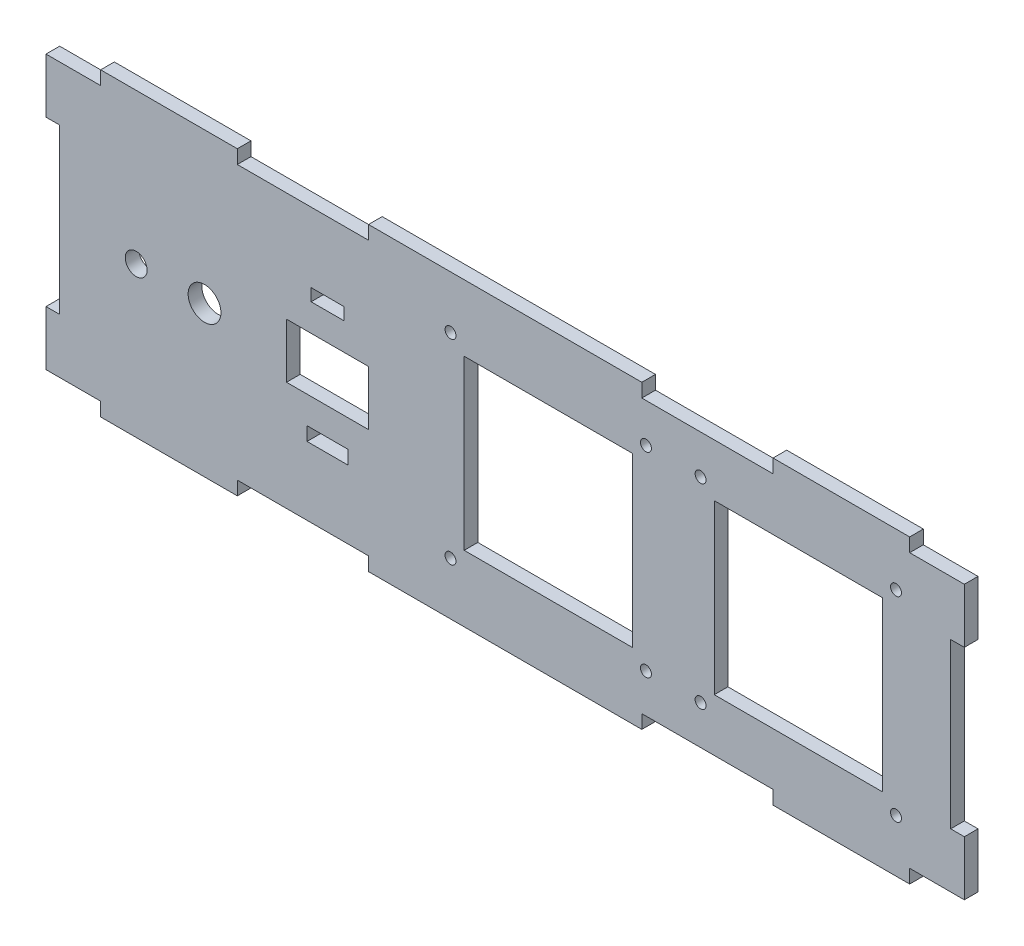
SolidWorks part; units mm, degrees
ref_plane "Front Plane" through (0, 0, 0) normal (0, 0, 1) x (1, 0, 0)
ref_plane "Top Plane" through (0, 0, 0) normal (0, 1, 0) x (1, 0, 0)
ref_plane "Right Plane" through (0, 0, 0) normal (1, 0, 0) x (0, 0, -1)
sketch "Sketch1" plane through (0, 0, 0) normal (0, 0, 1) x (1, 0, 0)
  line L0 (-168, 0) -> (168, 0) construction
  line L1 (168, -50) -> (-168, -50)
  line L2 (168, -50) -> (168, 50)
  line L3 (168, 50) -> (-168, 50)
  line L4 (-168, -50) -> (-168, 50)
  line L5 (168, -50) -> (-168, 50) construction
  line L6 (168, 50) -> (-168, -50) construction
  line L7 (0, 50) -> (0, -50) construction
  line L8 (-168, 30) -> (-163, 30)
  line L9 (-148, 50) -> (-98, 50)
  line L10 (-148, 50) -> (-148, 55)
  line L11 (-148, 55) -> (-98, 55)
  line L12 (-98, 50) -> (-98, 55)
  line L13 (0, 50) -> (-50, 50)
  line L15 (50, 55) -> (-50, 55)
  line L16 (-50, 50) -> (-50, 55)
  line L17 (-163, 30) -> (-163, -30)
  line L18 (-50, -50) -> (-50, -55)
  line L19 (50, -55) -> (-50, -55)
  line L20 (-168, -30) -> (-163, -30)
  line L21 (-148, -50) -> (-148, -55)
  line L22 (-98, -50) -> (-98, -55)
  line L23 (-148, -55) -> (-98, -55)
  line L24 (50, 50) -> (50, 55)
  line L25 (148, 50) -> (148, 55)
  line L26 (98, 50) -> (98, 55)
  line L27 (148, 55) -> (98, 55)
  line L28 (50, -50) -> (50, -55)
  line L29 (98, -50) -> (98, -55)
  line L30 (148, -50) -> (148, -55)
  line L31 (148, -55) -> (98, -55)
  line L32 (168, -30) -> (163, -30)
  line L33 (168, 30) -> (163, 30)
  line L34 (163, 30) -> (163, -30)
  line L35 (-50, 50) -> (50, 50)
  line L36 (-148, 50) -> (-98, 50)
  line L37 (98, 50) -> (148, 50)
  line L38 (168, 30) -> (168, -30)
  line L39 (148, -50) -> (98, -50)
  line L40 (50, -50) -> (-50, -50)
  line L41 (-98, -50) -> (-148, -50)
  line L42 (-168, 30) -> (-168, -30)
  line L54 (-20, 35.75) -> (51.5, -35.75) construction
  line L55 (-20, -35.75) -> (51.5, 35.75) construction
  line L56 (71.5, 35.75) -> (143, -35.75) construction
  line L57 (71.5, -35.75) -> (143, 35.75) construction
  line L58 (-65, 10) -> (-65, 35.75) construction
  line L59 (46.5, -30.75) -> (-15, -30.75)
  line L60 (46.5, -30.75) -> (46.5, 30.75)
  line L61 (46.5, 30.75) -> (-15, 30.75)
  line L62 (-15, -30.75) -> (-15, 30.75)
  line L63 (46.5, -30.75) -> (-15, 30.75) construction
  line L64 (46.5, 30.75) -> (-15, -30.75) construction
  line L65 (138, -30.75) -> (76.5, -30.75)
  line L66 (138, -30.75) -> (138, 30.75)
  line L67 (138, 30.75) -> (76.5, 30.75)
  line L68 (76.5, -30.75) -> (76.5, 30.75)
  line L69 (138, -30.75) -> (76.5, 30.75) construction
  line L70 (138, 30.75) -> (76.5, -30.75) construction
  line L71 (-80, -10) -> (-50, -10)
  line L72 (-80, -10) -> (-80, 10)
  line L73 (-80, 10) -> (-50, 10)
  line L74 (-50, -10) -> (-50, 10)
  line L75 (-80, -10) -> (-50, 10) construction
  line L76 (-80, 10) -> (-50, -10) construction
  line L77 (-71, 24.5) -> (-59, 24.5)
  line L81 (-71, 20) -> (-71, 24.5)
  line L82 (-71, 20) -> (-59, 20)
  line L83 (-65, 10) -> (-65, -50) construction
  line L84 (-65, 35.75) -> (-65, 50) construction
  line L85 (-57.5, -20) -> (-72.5, -20)
  line L86 (-72.5, -20) -> (-72.5, -25)
  line L87 (-72.5, -25) -> (-57.5, -25)
  line L88 (-57.5, -20) -> (-57.5, -25)
  line L89 (-59, 20) -> (-59, 24.5)
  circle A0 centre (-20, 35.75) radius 2
  circle A1 centre (51.5, 35.75) radius 2
  circle A2 centre (-20, -35.75) radius 2
  circle A3 centre (51.5, -35.75) radius 2
  circle A4 centre (71.5, 35.75) radius 2
  circle A5 centre (143, 35.75) radius 2
  circle A6 centre (71.5, -35.75) radius 2
  circle A7 centre (143, -35.75) radius 2
  circle A8 centre (-135, 0) radius 4
  circle A9 centre (-110, 0) radius 6
  point P0 (0, 0)
  point P24 (-163, 0)
  point P31 (0, 55)
  point P37 (0, -55)
  point P61 (15.75, 0)
  point P66 (107.25, 0)
  point P75 (-65, 0)
  point P86 (-65, 24.5)
  point P93 (-65, -25)
  point P94 (-65, -20)
  point P96 (-65, 20)
  dimension "D17" = 61.5
  dimension "D11" = 12
  dimension "D14" = 28
  dimension "D18" = 53
  dimension "D1" = 100
  dimension "D2" = 336
  dimension "D3" = 5
  dimension "D4" = 5
  dimension "D5" = 50
  dimension "D6" = 50
  dimension "D7" = 5
  dimension "D8" = 30
  dimension "D9" = 20
  dimension "D10" = 20
  dimension "D12" = 71.5
  dimension "D13" = 71.5
  dimension "D15" = 71.5
  dimension "D16" = 71.5
  dimension "D19" = 30
  dimension "D20" = 20
  dimension "D21" = 30
  dimension "D22" = 4.5
  dimension "D23" = 6
  dimension "D24" = 10
  dimension "D25" = 7.5
  dimension "D26" = 5
  dimension "D27" = 10
extrude "Boss-Extrude1" add sketch "Sketch1" along normal blind 5 contours L34 L33 L2 L3 L4 L8 L17 L20 L1 L32 | L28 L1 L18 L19 | L31 L30 L1 L29 | L25 L27 L26 L3 | L3 L12 L11 L10 | L23 L22 L41 L21 | L35 L24 L15 L16 region at (-16.5607, 0.0199, 0) region at (123, -52.5, 0) region at (0, -52.5, 0) region at (123, 52.5, 0) region at (-123, 52.5, 0)
